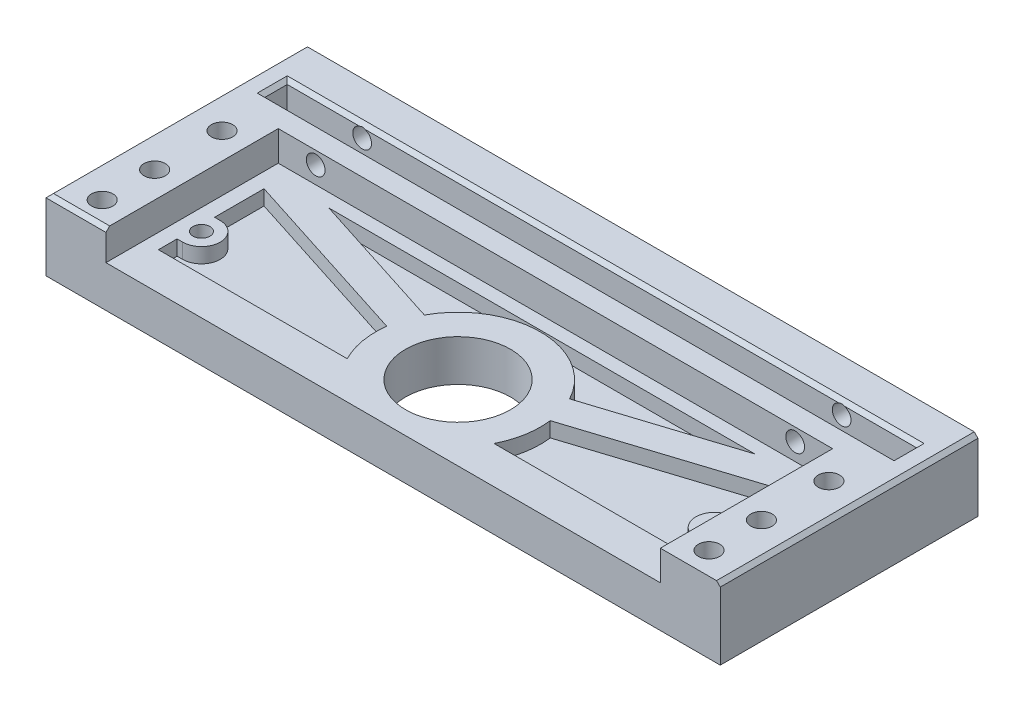
SolidWorks part; units mm, degrees
ref_plane "Front Plane" through (0, 0, 0) normal (0, 0, 1) x (1, 0, 0)
ref_plane "Top Plane" through (0, 0, 0) normal (0, 1, 0) x (1, 0, 0)
ref_plane "Right Plane" through (0, 0, 0) normal (1, 0, 0) x (0, 0, -1)
sketch "Sketch1" plane through (0, 0, 0) normal (0, 0, 1) x (1, 0, 0)
  line L1 (0, 0) -> (90, 0)
  line L2 (0, 0) -> (0, 9.525)
  line L3 (0, 9.525) -> (90, 9.525)
  line L4 (90, 0) -> (90, 9.525)
  circle A0 centre (30, 4.7625) radius 2
  circle A1 centre (60, 4.7625) radius 2
  point P7 (0, 4.7625)
  point P11 (45, 0)
  dimension "D5" = 4
  dimension "D1" = 90
  dimension "D2" = 9.525
  dimension "D3" = 15
  dimension "D4" = 15
extrude "Boss-Extrude1" add sketch "Sketch1" along normal blind 45 contours A1 | A0 | L1 L4 L3 L2 A1 A0
sketch "Sketch2" plane through (0, 9.525, 0) normal (0, 1, 0) x (1, 0, 0)
  line L0 (0, 0) -> (90, 0) construction
  circle A0 centre (45, -35) radius 7
  point P4 (45, 0)
  dimension "D2" = 14
  dimension "D1" = 35
extrude "Cut-Extrude2" cut sketch "Sketch2" against normal blind 10
sketch "Sketch3" plane through (0, 9.525, 0) normal (0, 1, 0) x (1, 0, 0)
  line L0 (90, -45) -> (90, 0) construction
  line L1 (0, -45) -> (0, 0) construction
  circle A0 centre (85.5, -35) radius 1.4224
  circle A1 centre (4.5, -35) radius 1.4224
  circle A2 centre (45, -35) radius 7 construction
  circle A3 centre (45, -35) radius 7
  circle A4 centre (85.5, -26) radius 1.4224
  circle A5 centre (4.5, -26) radius 1.4224
  circle A6 centre (79.25, -35) radius 1.1303
  circle A7 centre (10.75, -35) radius 1.1303
  dimension "D1" = 2.8448
  dimension "D8" = 34.25
  dimension "D9" = 2.2606
  dimension "D2" = 4.5
  dimension "D3" = 4.5
  dimension "D5" = 9
  dimension "D6" = 0
  dimension "D7" = 34.25
  dimension "D4" = 2
extrude "Cut-Extrude3" cut sketch "Sketch3" against normal blind 10
sketch "Sketch4" plane through (0, 9.525, 0) normal (0, 1, 0) x (1, 0, 0)
  line L1 (87, -15.8) -> (3, -15.8)
  line L2 (87, -15.8) -> (87, -18.8)
  line L3 (87, -18.8) -> (3, -18.8)
  line L4 (3, -15.8) -> (3, -18.8)
  line L6 (90, -45) -> (90, 0) construction
  line L7 (0, -45) -> (0, 0) construction
  circle A0 centre (45, -35) radius 7 construction
  dimension "D1" = 16.2
  dimension "D2" = 3
  dimension "D3" = 3
  dimension "D4" = 3
extrude "Cut-Extrude4" cut sketch "Sketch4" against normal blind 6
sketch "Sketch6" plane through (0, 9.525, 0) normal (0, 1, 0) x (1, 0, 0)
  line L0 (10.75, -37.5) -> (10, -37.5)
  line L1 (10.75, -32.5) -> (10, -32.5)
  line L2 (79.25, -37.5) -> (80, -37.5)
  line L3 (79.25, -32.5) -> (80, -32.5)
  line L4 (80, -32.5) -> (80, -23.8)
  line L5 (54.798, -40) -> (80, -40)
  line L6 (80, -40) -> (80, -37.5)
  line L7 (80, -23.8) -> (10, -23.8)
  line L8 (10, -23.8) -> (10, -32.5)
  line L9 (90, -45) -> (90, 0)
  line L10 (90, 0) -> (0, 0)
  line L11 (0, 0) -> (0, -45)
  line L12 (0, -45) -> (90, -45)
  line L13 (90, -45) -> (90, 0)
  line L15 (0, 0) -> (0, -45)
  line L16 (0, -45) -> (90, -45)
  line L17 (10, -40) -> (35.202, -40)
  line L18 (3, -18.8) -> (87, -18.8) construction
  line L19 (80, -23.8) -> (45, -35) construction
  line L20 (45, -35) -> (10, -23.8) construction
  line L21 (80, -25.8999) -> (55.9116, -33.6082)
  line L22 (73.4378, -23.8) -> (54.6925, -29.7985)
  line L23 (35.3075, -29.7985) -> (16.5622, -23.8)
  line L24 (34.0884, -33.6082) -> (10, -25.8999)
  line L25 (10, -37.5) -> (10, -40)
  line L29 (90, 0) -> (0, 0)
  arc A0 (10.75, -37.5) -> (10.75, -32.5) centre (10.75, -35) ccw
  circle A1 centre (45, -35) radius 11
  arc A2 (79.25, -32.5) -> (79.25, -37.5) centre (79.25, -35) ccw
  dimension "D2" = 22
  dimension "D11" = 5
  dimension "D12" = 5
  dimension "D3" = 5
  dimension "D4" = 10
  dimension "D5" = 5
  dimension "D6" = 10
  dimension "D7" = 2
  dimension "D8" = 4
  dimension "D9" = 2
  dimension "D10" = 4
  dimension "D1" = 0
extrude "Cut-Extrude6" cut sketch "Sketch6" against normal blind 6 and the other way through all contours A1 L5 L6 L21 | A1 L22 L7 L23 | A1 L24 L8 L17
sketch "Sketch7" plane through (0, 9.525, 0) normal (0, 1, 0) x (1, 0, 0)
  line L0 (0, -45) -> (0, 0) construction
  line L1 (90, 0) -> (0, 0)
  line L2 (90, 0) -> (90, -3)
  line L3 (90, -3) -> (0, -3)
  line L4 (0, 0) -> (0, -3)
  dimension "D1" = 3
extrude "Cut-Extrude7" cut sketch "Sketch7" against normal blind 10
sketch "Sketch9" plane through (0, 9.525, 0) normal (0, 1, 0) x (1, 0, 0)
  line L0 (0, -45) -> (90, -45) construction
  line L1 (82, -45) -> (8, -45)
  line L2 (82, -45) -> (82, -22)
  line L3 (82, -22) -> (8, -22)
  line L4 (8, -45) -> (8, -22)
  line L5 (90, -45) -> (90, -3) construction
  line L6 (0, -45) -> (0, -3) construction
  line L7 (0, -3) -> (90, -3) construction
  dimension "D1" = 8
  dimension "D2" = 8
  dimension "D3" = 19
extrude "Cut-Extrude8" cut sketch "Sketch9" against normal blind 4
sketch "Sketch10" plane through (0, 0, 22) normal (0, 0, 1) x (1, 0, 0)
  line L0 (82, 5.525) -> (82, 9.525) construction
  line L1 (8, 5.525) -> (8, 9.525) construction
  line L2 (82, 9.525) -> (8, 9.525) construction
  circle A0 centre (77, 7.825) radius 1.25
  circle A1 centre (13, 7.825) radius 1.25
  dimension "D1" = 2.5
  dimension "D2" = 5
  dimension "D3" = 5
  dimension "D4" = 1.7
extrude "Cut-Extrude9" cut sketch "Sketch10" against normal up to surface (19 mm away) up to face at (45, 4.7625, 3)
chamfer "Chamfer2" distance 0.5 angle 45 7 edges at (45, 9.525, 3) (87, 9.525, 17.3) (45, 9.525, 15.8) (3, 9.525, 17.3) (45, 9.525, 18.8) (0, 9.525, 24) (90, 9.525, 24)
sketch "Sketch11" plane through (0, 9.525, 0) normal (0, 1, 0) x (1, 0, 0)
  circle A0 centre (85.5, -42) radius 1.4224
  circle A1 centre (85.5, -35) radius 1.4224 construction
  circle A2 centre (85.5, -35) radius 1.4224
  circle A3 centre (4.5, -42) radius 1.4224
  circle A4 centre (4.5, -35) radius 1.4224 construction
  circle A5 centre (4.5, -35) radius 1.4224
  dimension "D2" = 2.8448
  dimension "D1" = 7
extrude "Cut-Extrude10" cut sketch "Sketch11" against normal blind 10 contours A0 | A3
sketch "Sketch12" plane through (0, 9.525, 0) normal (0, 1, 0) x (1, 0, 0)
  line L6 (2.5, -15.3) -> (87.5, -15.3) construction
  line L7 (91.3303, 10.2707) -> (-8.7648, 10.2707)
  line L8 (91.3303, 10.2707) -> (91.3303, -10.6)
  line L9 (91.3303, -10.6) -> (-8.7648, -10.6)
  line L10 (-8.7648, 10.2707) -> (-8.7648, -10.6)
  dimension "D1" = 4.7
extrude "Cut-Extrude11" cut sketch "Sketch12" against normal blind 10
